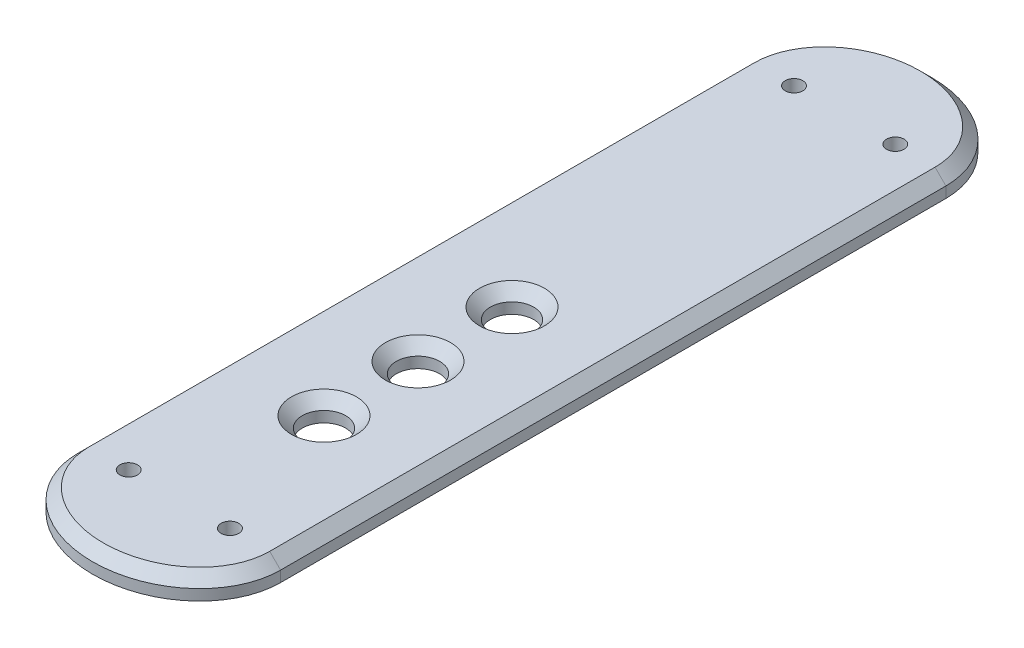
SolidWorks part; units mm, degrees
ref_plane "Front Plane" through (0, 0, 0) normal (0, 0, 1) x (1, 0, 0)
ref_plane "Top Plane" through (0, 0, 0) normal (0, 1, 0) x (1, 0, 0)
ref_plane "Right Plane" through (0, 0, 0) normal (1, 0, 0) x (0, 0, -1)
sketch "Sketch3" plane through (0, 0, 0) normal (0, 1, 0) x (1, 0, 0)
  line L0 (-7, 0) -> (7, 0) construction
  line L4 (-7, -23) -> (-7, 23)
  line L5 (0, -29) -> (0, 29) construction
  line L6 (7, -23) -> (7, 23)
  circle A0 centre (-3.5, 23) radius 0.61
  circle A1 centre (-3.5, 23) radius 1.5
  circle A2 centre (3.5, 23) radius 1.5
  circle A3 centre (3.5, 23) radius 0.61
  circle A4 centre (3.5, -23) radius 0.61
  circle A5 centre (3.5, -23) radius 1.5
  circle A6 centre (-3.5, -23) radius 1.5
  circle A7 centre (-3.5, -23) radius 0.61
  ellipse E0 centre (0, 23) end of major axis (-7, 23) minor radius 6 (7, 23) -> (-7, 23) ccw
  ellipse E1 centre (0, -23) end of major axis (-7, -23) minor radius 6 (7, -23) -> (-7, -23) cw
  point P20 (0, 0)
  dimension "D1" = 1.22
  dimension "D6" = 3
  dimension "D2" = 3.5
  dimension "D3" = 23
  dimension "D4" = 29
  dimension "D5" = 7
extrude "Boss-Extrude2" add sketch "Sketch3" against normal blind 1.5 contours L4 E0 L6 E1
extrude "Cut-Extrude1" cut sketch "Sketch3<3>" against normal through all contours A7 | A4 | A0 | A3
sketch "Sketch3<3>" plane through (0, 0, 0) normal (0, 1, 0) x (1, 0, 0) same geometry as "Sketch3"
chamfer "Chamfer2" distance 0.75 angle 45 4 edges at (7, 0, 0) (0, 0, 29) (0, 0, -29) (-7, 0, 0)
sketch "Sketch6" plane through (0, 0, 0) normal (0, 1, 0) x (1, 0, 0)
  line L0 (0, 11.45) -> (0, 14.1085)
  line L1 (0.2205, 14.1892) -> (1.4045, 12.7884)
  line L2 (1.5955, 12.7884) -> (2.7795, 14.1892)
  line L3 (3, 14.1085) -> (3, 11.45)
  line L4 (-3, 11.45) -> (3, 11.45) construction
  line L13 (-2.6427, 21.5) -> (2.6427, 21.5) construction
  line L14 (2.6427, 21.5) -> (0, 21.5) construction
  line L15 (0, 21.5) -> (0, 0) construction
  circle A0 centre (0, 12.2) radius 4.5
  arc A2 (-3, 11.45) -> (0, 11.45) centre (-1.5, 11.45) ccw
  arc A3 (3, 14.1085) -> (2.7795, 14.1892) centre (2.875, 14.1085) ccw
  arc A4 (1.5955, 12.7884) -> (1.4045, 12.7884) centre (1.5, 12.8691) cw
  arc A5 (0.2205, 14.1892) -> (0, 14.1085) centre (0.125, 14.1085) ccw
  point P4 (0, 0)
  point P11 (-0.9363, 0)
  point P14 (0.05, 12.1262)
  point P16 (3, 14.45)
  point P19 (1.5, 12.6755)
  point P22 (0, 14.45)
  dimension "D1" = 9
  dimension "D2" = 3
  dimension "D7" = 0.125
  dimension "D3" = 3
  dimension "D4" = 3
  dimension "D5" = 1.5
  dimension "D6" = 0.75
  dimension "D9" = 9.3
  dimension "D11" = 21.5
sketch "Sketch8" plane through (0, 0, 0) normal (0, 1, 0) x (1, 0, 0)
  line L0 (0, -29) -> (0, 29) construction
  line L1 (1.5, 0) -> (1.5, -13) construction
  line L2 (0, -1.5) -> (0, -5) construction
  line L3 (0, -5) -> (0, -8) construction
  line L4 (0, -8) -> (0, -11.5) construction
  line L5 (0, -11.5) -> (0, -14.5) construction
  circle A0 centre (0, 0) radius 1.5
  circle A1 centre (0, -6.5) radius 1.5
  circle A2 centre (0, -13) radius 1.5
  dimension "D1" = 1.5
  dimension "D2" = 3.5
  dimension "D3" = 3.5
extrude "Cut-Extrude5" cut sketch "Sketch8" against normal through all
chamfer "Chamfer3" distance 0.75 angle 45 3 edges at (0, 0, 14.5) (0, 0, 8) (0, 0, 1.5)
